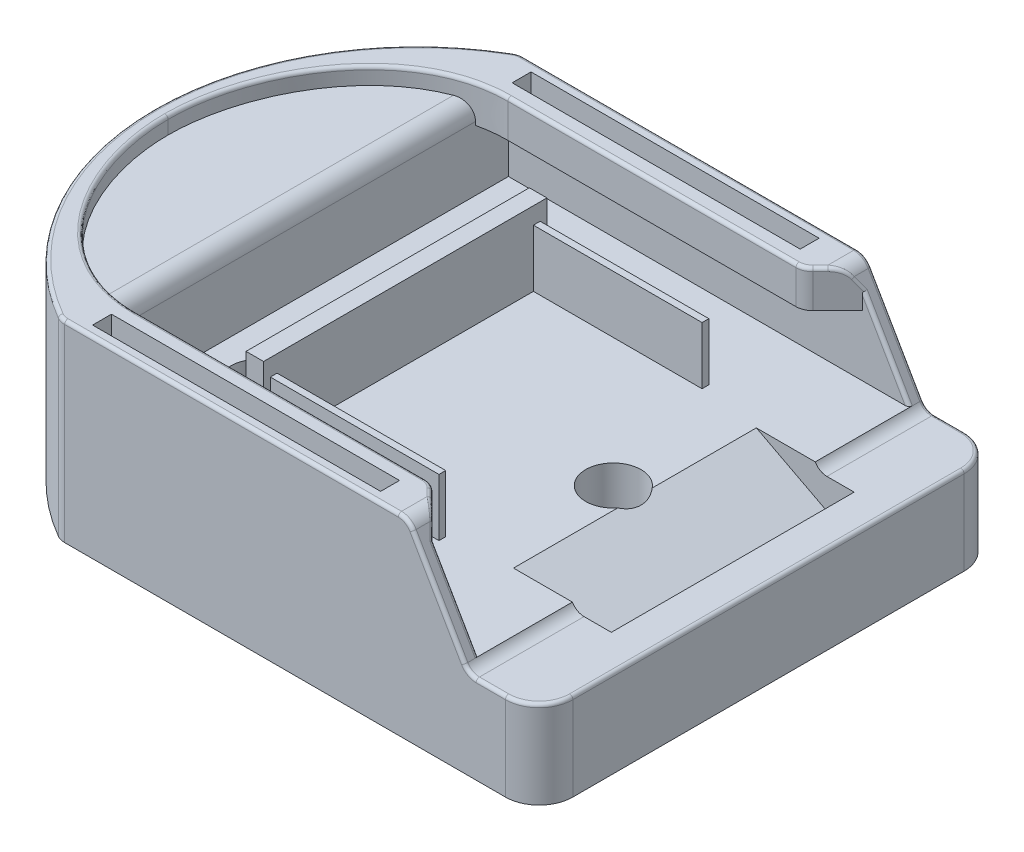
SolidWorks part; units mm, degrees
ref_plane "Front Plane" through (0, 0, 0) normal (0, 0, 1) x (1, 0, 0)
ref_plane "Top Plane" through (0, 0, 0) normal (0, 1, 0) x (1, 0, 0)
ref_plane "Right Plane" through (0, 0, 0) normal (1, 0, 0) x (0, 0, -1)
sketch "Sketch1" plane through (0, 0, 0) normal (0, 1, 0) x (1, 0, 0)
  line L0 (-128.2391, 0) -> (113.4565, 0) construction
  line L1 (-45.5, 34) -> (45.5, 34)
  line L2 (-45.5, 34) -> (-45.5, -34)
  line L3 (-45.5, -34) -> (45.5, -34)
  line L4 (45.5, 34) -> (45.5, -34)
  line L5 (-45.5, 34) -> (45.5, -34) construction
  line L6 (-45.5, -34) -> (45.5, 34) construction
  circle A0 centre (-6.6, 0) radius 38.9
  point P0 (0, 0)
  point P10 (-25.5, 34)
  dimension "D1" = 68
  dimension "D2" = 91
  dimension "D3" = 20
extrude "Boss-Extrude1" add sketch "Sketch1" along normal blind 14 contours L3 A0 L1 | A0 L3 L4 L1 region at (-6.6, 0, 0) region at (35.1839, 0, 0)
sketch "Sketch2" plane through (0, 14, 0) normal (0, 1, 0) x (1, 0, 0)
  line L0 (-24.9475, -31.9) -> (43.4, -31.9)
  line L1 (43.4, -31.9) -> (43.4, 31.9)
  line L2 (43.4, 31.9) -> (-24.9475, 31.9)
  line L3 (-25.5, -34) -> (45.5, -34)
  line L4 (45.5, -34) -> (45.5, 34)
  line L5 (45.5, 34) -> (-25.5, 34)
  line L6 (-25.5, -34) -> (45.5, -34)
  line L7 (45.5, -34) -> (45.5, 34)
  line L8 (45.5, 34) -> (-25.5, 34)
  line L9 (-24.9475, 31.9) -> (-24.9475, -31.9)
  arc A0 (-24.9475, 31.9) -> (-24.9475, -31.9) centre (-6.6, 0) ccw
  arc A1 (-25.5, 34) -> (-25.5, -34) centre (-6.6, 0) ccw
  arc A2 (-25.5, 34) -> (-25.5, -34) centre (-6.6, 0) ccw
  point P12 (-45.5, 0)
  line M10 (-25.5, -34) -> (45.5, -34)
  line M11 (45.5, -34) -> (45.5, 34)
  line M12 (45.5, 34) -> (-25.5, 34)
  arc M13 (-25.5, 34) -> (-25.5, -34) centre (-6.6, 0) ccw
  dimension "D1" = 0
  dimension "D2" = 2.1
extrude "Boss-Extrude2" add sketch "Sketch2" along normal blind 12 contours A0 L2 L1 L0 M13 M10 M11 M12 | L9 A0 region at (-32.5144, 14, 0) region at (-44.364, 14, 0)
sketch "Sketch3" plane through (0, 0, 34) normal (0, 0, 1) x (1, 0, 0)
  line L2 (27.5, 26) -> (35.0056, 13)
  line L3 (-25.5, 26) -> (45.5, 26) construction
  line L4 (35.0056, 13) -> (45.5, 13)
  line L6 (45.5, 13) -> (45.5, 26)
  line L7 (45.5, 26) -> (27.5, 26)
  line L8 (-25.5, 0) -> (45.5, 0) construction
  dimension "D1" = 18
  dimension "D2" = 60
  dimension "D3" = 13
extrude "Cut-Extrude1" cut sketch "Sketch3" against normal up to next
sketch "Sketch4" plane through (0, 26, 0) normal (0, 1, 0) x (1, 0, 0)
  line L0 (27.5, 31.9) -> (23.1, 27.5)
  line L1 (23.1, 27.5) -> (-20.6204, 27.5)
  line L2 (-45.5, 0) -> (45.5, 0) construction
  line L3 (45.5, 34) -> (45.5, -34) construction
  line L4 (-43.5, 0) -> (-43.5, -34) construction
  line L5 (-25.5, -34) -> (27.5, -34) construction
  line L6 (27.5, 34) -> (-25.5, 34) construction
  line L7 (27.5, 31.9) -> (-24.9475, 31.9) construction
  line L8 (27.5, -31.9) -> (23.1, -27.5)
  line L9 (23.1, -27.5) -> (-20.6204, -27.5)
  line L15 (27.5, 31.9) -> (27.5, 34)
  line L16 (27.5, 34) -> (-25.5, 34)
  line L17 (-25.5, -34) -> (27.5, -34)
  line L18 (27.5, -34) -> (27.5, -31.9)
  line L19 (27.5, -31.9) -> (-24.9475, -31.9)
  line L20 (-24.9475, -31.9) -> (-24.9475, 31.9)
  line L21 (-24.9475, 31.9) -> (27.5, 31.9)
  line L22 (27.5, 31.9) -> (27.5, 34)
  line L23 (27.5, 34) -> (-25.5, 34)
  line L24 (-25.5, -34) -> (27.5, -34)
  line L25 (27.5, -34) -> (27.5, -31.9)
  line L26 (27.5, -31.9) -> (-24.9475, -31.9)
  line L27 (-24.9475, -31.9) -> (-24.9475, 31.9)
  line L28 (-24.9475, 31.9) -> (27.5, 31.9)
  arc A0 (-25.5, 34) -> (-25.5, -34) centre (-6.6, 0) ccw construction
  arc A2 (-25.5, 34) -> (-25.5, -34) centre (-6.6, 0) ccw
  arc A3 (-25.5, 34) -> (-25.5, -34) centre (-6.6, 0) ccw
  spline S0 degree 3 poles (-20.6204, 27.5) (-34.6798, 27.5) (-43.5, 12.6875) (-43.5, 0) knots 0 0 0 0 1 1 1 1
  spline S1 degree 3 poles (-20.6204, -27.5) (-34.6798, -27.5) (-43.5, -12.6875) (-43.5, 0) knots 0 0 0 0 1 1 1 1
  line M13 (27.5, 31.9) -> (27.5, 34)
  line M14 (27.5, 34) -> (-25.5, 34)
  arc M15 (-25.5, 34) -> (-25.5, -34) centre (-6.6, 0) ccw
  line M16 (-25.5, -34) -> (27.5, -34)
  line M17 (27.5, -34) -> (27.5, -31.9)
  line M18 (27.5, -31.9) -> (-24.9475, -31.9)
  line M19 (-24.9475, -31.9) -> (-24.9475, 31.9)
  line M20 (-24.9475, 31.9) -> (27.5, 31.9)
  dimension "D1" = 2
  dimension "D2" = 6.5
  dimension "D3" = 45
  dimension "D4" = 0
extrude "Boss-Extrude3" add sketch "Sketch4" along normal blind 2.5 contours S0 L1 L0 L27 M20 | S1 S0 L27 M19 M20 M13 M14 M15 M16 M17 M18 | L9 S1 L8 M19 M18 region at (1.2763, 26, -32.8976) region at (0.1168, 26, -29.7247) region at (0.1168, 26, 29.7247)
sketch "Sketch5" plane through (0, 0, 0) normal (0, -1, 0) x (1, 0, 0)
  line L0 (-45.5, 0) -> (45.5, 0) construction
  line L1 (45.5, -34) -> (45.5, 34) construction
  line L2 (-17.1218, 34) -> (-17.1218, -34) construction
  line L3 (-25.5, 34) -> (45.5, 34) construction
  line L4 (-25.5, -34) -> (45.5, -34) construction
  arc A0 (-25.5, 34) -> (-25.5, -34) centre (-6.6, 0) ccw construction
  circle A1 centre (22.5, 0) radius 1.75
  circle A2 centre (-17.1218, 13) radius 1.75
  circle A3 centre (-17.1218, -13) radius 1.75
  dimension "D1" = 3.5
  dimension "D2" = 23
  dimension "D3" = 26
  dimension "D4" = 41.7
extrude "Cut-Extrude2" cut sketch "Sketch5" against normal up to next
sketch "Sketch6" plane through (0, 14, 0) normal (0, 1, 0) x (1, 0, 0)
  circle A0 centre (-17.1218, 13) radius 4.1
  circle A1 centre (-17.1218, -13) radius 4.1
  circle A2 centre (22.5, 0) radius 4.1
  dimension "D1" = 8.2
extrude "Cut-Extrude3" cut sketch "Sketch6" against normal blind 10
sketch "Sketch7" plane through (0, 26, 0) normal (0, -1, 0) x (1, 0, 0)
  line L4 (-24.9475, -27.0124) -> (-24.9475, -31.9)
  line L5 (-24.9475, -31.9) -> (27.5, -31.9)
  line L6 (27.5, -31.9) -> (23.1, -27.5)
  line L7 (23.1, -27.5) -> (-20.6204, -27.5)
  line L8 (-24.9475, -27.0124) -> (-24.9475, -31.9)
  line L9 (-24.9475, -31.9) -> (27.5, -31.9)
  line L10 (27.5, -31.9) -> (23.1, -27.5)
  line L11 (23.1, -27.5) -> (-20.6204, -27.5)
  line L12 (27.5, 31.9) -> (-24.9475, 31.9)
  line L13 (-24.9475, 31.9) -> (-24.9475, 27.0124)
  line L14 (-20.6204, 27.5) -> (23.1, 27.5)
  line L15 (23.1, 27.5) -> (27.5, 31.9)
  line L16 (27.5, 31.9) -> (-24.9475, 31.9)
  line L17 (-24.9475, 31.9) -> (-24.9475, 27.0124)
  line L18 (-20.6204, 27.5) -> (23.1, 27.5)
  line L19 (23.1, 27.5) -> (27.5, 31.9)
  spline S1 degree 3 poles (100.5467, 3955.0954) (522.8146, -4176.4929) (-1226.7011, 4047.0875) (1672.3793, -3632.5256) knots -5.410058 -5.410058 -5.410058 -5.410058 6.985464 6.985464 6.985464 6.985464 only from (-20.6204, -27.5) to (-24.9475, -27.0124)
  spline S2 degree 3 poles (-20.6204, -27.5) (-22.1242, -27.5) (-23.568, -27.3305) (-24.9475, -27.0124) knots 0 0 0 0 0.106957 0.106957 0.106957 0.106957
  spline S3 degree 3 poles (1672.4087, 3632.6034) (-1226.7052, -4047.1225) (522.8067, 4176.4764) (100.5501, -3955.0302) knots -6.878548 -6.878548 -6.878548 -6.878548 5.516982 5.516982 5.516982 5.516982 only from (-24.9475, 27.0124) to (-20.6204, 27.5)
  spline S4 degree 3 poles (-24.9475, 27.0124) (-23.568, 27.3305) (-22.1242, 27.5) (-20.6204, 27.5) knots 0 0 0 0 0.106957 0.106957 0.106957 0.106957
  dimension "D1" = 0
  dimension "D2" = 0
extrude "Boss-Extrude4" add sketch "Sketch7" along normal offset from surface (3 mm away) 5.5 up to face at (2.1217, 28.5, 0)
sketch "Sketch8" plane through (0, 14, 0) normal (0, 1, 0) x (1, 0, 0)
  line L0 (-9.6475, 27.5) -> (-9.6475, -27.5) construction
  line L1 (23.1, 27.5) -> (-20.6204, 27.5) construction
  line L2 (23.1, -27.5) -> (-20.6204, -27.5) construction
  line L3 (-24.9475, 27.0124) -> (-24.9475, -27.0124) construction
  line L4 (-10.9475, 21) -> (-8.3475, 21)
  line L5 (-10.9475, 21) -> (-10.9475, -21)
  line L6 (-10.9475, -21) -> (-8.3475, -21)
  line L7 (-8.3475, 21) -> (-8.3475, -21)
  line L8 (-10.9475, 21) -> (-8.3475, -21) construction
  line L9 (-10.9475, -21) -> (-8.3475, 21) construction
  point P6 (-9.6475, 0)
  dimension "D1" = 2.6
  dimension "D2" = 14
  dimension "D3" = 42
extrude "Boss-Extrude5" add sketch "Sketch8" along normal blind 11
sketch "Sketch9" plane through (0, 14, 0) normal (0, 1, 0) x (1, 0, 0)
  line L0 (-54.9878, 0) -> (54.0951, 0) construction
  line L1 (-8.3475, -21) -> (-8.3475, 21) construction
  line L2 (-8.3475, 20) -> (16.6525, 20)
  line L3 (-8.3475, 20) -> (-8.3475, 19)
  line L4 (-8.3475, 19) -> (16.6525, 19)
  line L5 (16.6525, 20) -> (16.6525, 19)
  line L6 (-8.3475, -20) -> (-8.3475, -19)
  line L7 (-8.3475, -19) -> (16.6525, -19)
  line L8 (16.6525, -20) -> (16.6525, -19)
  line L9 (-8.3475, -20) -> (16.6525, -20)
  dimension "D1" = 1
  dimension "D2" = 25
  dimension "D3" = 38
extrude "Boss-Extrude6" add sketch "Sketch9" along normal blind 8.5
sketch "Sketch10" plane through (0, 28.5, 0) normal (0, 1, 0) x (1, 0, 0)
  line L0 (27.5, 34) -> (27.5, 31.9) construction
  line L1 (20.5, 32.5) -> (-22.2, 32.5)
  line L2 (20.5, 32.5) -> (20.5, 29.7)
  line L3 (20.5, 29.7) -> (-22.2, 29.7)
  line L4 (-22.2, 32.5) -> (-22.2, 29.7)
  line L5 (27.5, 34) -> (-25.5, 34) construction
  line L6 (-53.6308, 0) -> (57.3197, 0) construction
  line L7 (20.5, -32.5) -> (20.5, -29.7)
  line L8 (20.5, -32.5) -> (-22.2, -32.5)
  line L9 (-22.2, -32.5) -> (-22.2, -29.7)
  line L10 (20.5, -29.7) -> (-22.2, -29.7)
  dimension "D1" = 7
  dimension "D2" = 2.8
  dimension "D3" = 1.5
  dimension "D4" = 42.7
extrude "Cut-Extrude4" cut sketch "Sketch10" against normal blind 3.8
fillet "Fillet1" radius 2 1 edges at (35.0056, 13, 0)
sketch "Sketch11" plane through (0, 0, 0) normal (0, 0, 1) x (1, 0, 0)
  line L0 (36.1603, 13) -> (45.5, 13) construction
  line L1 (36.1603, 13) -> (45.5, 13)
  line L2 (34.4282, 14) -> (25.7, 14)
  line L3 (25.7, 14) -> (37.2, 8)
  line L4 (37.2, 8) -> (40.2, 8)
  line L5 (40.2, 8) -> (40.2, 13)
  line L6 (45.5, 13) -> (45.5, 0) construction
  arc A0 (34.4282, 14) -> (36.1603, 13) centre (36.1603, 15) ccw construction
  arc A1 (34.4282, 14) -> (36.1603, 13) centre (36.1603, 15) ccw
  dimension "D1" = 14.5
  dimension "D2" = 5.3
  dimension "D3" = 5
  dimension "D4" = 3
extrude "Cut-Extrude5" cut sketch "Sketch11" against normal mid plane 36 contours A1 L2 L3 L4 L5 L1 region at (34.9325, 11.4493, 0)
sketch "Sketch12" plane through (0, 0, 34) normal (0, 0, 1) x (1, 0, 0)
  line L0 (27.5, 26) -> (26.0566, 28.5)
  line L1 (-25.5, 28.5) -> (27.5, 28.5) construction
  line L2 (27.5, 26) -> (34.4282, 14) construction
  line L3 (26.0566, 28.5) -> (27.5, 28.5)
  line L4 (27.5, 28.5) -> (27.5, 26)
extrude "Cut-Extrude6" cut sketch "Sketch12" against normal through all
fillet "Fillet2" radius 5 2 edges at (45.5, 6.5, -34) (45.5, 6.5, 34)
fillet "Fillet3" radius 2.5 7 edges at (-24.9475, 26, 0) (23.1, 25.75, 27.5) (23.1, 25.75, -27.5) (26.0566, 28.5, -32.2283) (26.0566, 28.5, 32.2283) (-25.5, 14.25, -34) (-25.5, 14.25, 34)
fillet "Fillet4" radius 0.5 30 edges at (27.1392, 26.625, -31.5392) (25.8632, 28.1651, -30.2632) (24.2227, 28.5, -28.6227) (23.0212, 28.5, -27.6903) (0.722, 28.5, -27.5) (27.1392, 26.625, 31.5392) (25.8632, 28.1651, 30.2632) (24.2227, 28.5, 28.6227) (23.0212, 28.5, 27.6903) (0.722, 28.5, 27.5) (25.8632, 28.1651, 34) (-0.1135, 28.5, 34) (-25.4889, 28.5, 33.9144) (-45.5, 28.5, 0) (-25.4889, 28.5, -33.9144) (-0.1135, 28.5, -34) (25.8632, 28.1651, -34) (30.6033, 20.625, -34) (35.1603, 13.2679, -34) (38.3301, 13, -34) (44.0355, 13, -32.5355) (45.5, 13, 0) (44.0355, 13, 32.5355) (38.3301, 13, 34) (35.1603, 13.2679, 34) (30.9641, 20, -31.9) (30.9641, 20, 31.9) (30.6033, 20.625, 34)
ref_axis "Axis1" through (22.5, 4, 0) along (0, -1, 0)
ref_axis "Axis2" through (-17.1218, 4, 13) along (0, -1, 0)
ref_axis "Axis3" through (-17.1218, 4, -13) along (0, -1, 0)
ref_plane "Plane1" through (22.5, 0, 0) normal (1, 0, 0) x (0, 0, -1)
ref_plane "Plane2" through (-17.1218, 0, 0) normal (1, 0, 0) x (0, 0, -1)
